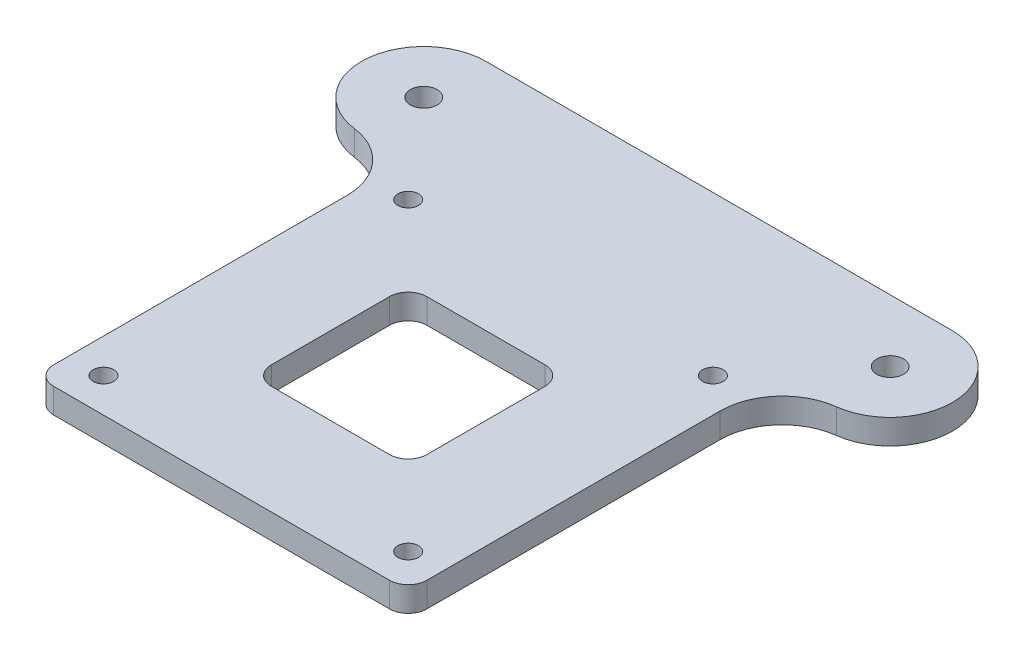
SolidWorks part; units mm, degrees
ref_plane "前视基准面" through (0, 0, 0) normal (0, 0, 1) x (1, 0, 0)
ref_plane "上视基准面" through (0, 0, 0) normal (0, 1, 0) x (1, 0, 0)
ref_plane "右视基准面" through (0, 0, 0) normal (1, 0, 0) x (0, 0, -1)
sketch "Sketch1" plane through (0, 0, 0) normal (0, 1, 0) x (1, 0, 0)
  line L1 (-24.5, -24.5) -> (24.5, -24.5) construction
  line L2 (-24.5, -24.5) -> (-24.5, 24.5) construction
  line L3 (-24.5, 24.5) -> (24.5, 24.5) construction
  line L4 (24.5, -24.5) -> (24.5, 24.5) construction
  line L5 (-24.5, -24.5) -> (24.5, 24.5) construction
  line L6 (-24.5, 24.5) -> (24.5, -24.5) construction
  line L7 (-30, -30) -> (30, -30)
  line L8 (-30, -30) -> (-30, 30)
  line L9 (-30, 30) -> (30, 30)
  line L10 (30, -30) -> (30, 30)
  line L11 (-30, -30) -> (30, 30) construction
  line L12 (-30, 30) -> (30, -30) construction
  circle A0 centre (-24.5, 24.5) radius 1.65
  circle A1 centre (24.5, 24.5) radius 1.65
  circle A2 centre (-24.5, -24.5) radius 1.65
  circle A3 centre (24.5, -24.5) radius 1.65
  point P0 (0, 0)
  point P6 (0, 0)
  dimension "D3" = 3.3
  dimension "D1" = 49
  dimension "D2" = 60
extrude "Boss-Extrude1" add sketch "Sketch1" along normal blind 4
sketch "Sketch2" plane through (0, 4, 0) normal (0, 1, 0) x (1, 0, 0)
  line L0 (-37.5, 40) -> (37.5, 40) construction
  line L1 (-37.5, 50) -> (37.5, 50)
  line L2 (-37.5, 30) -> (37.5, 30)
  line L4 (30, 30) -> (-30, 30) construction
  arc A0 (-37.5, 50) -> (-37.5, 30) centre (-37.5, 40) ccw
  arc A1 (37.5, 30) -> (37.5, 50) centre (37.5, 40) ccw
  circle A2 centre (-37.5, 40) radius 2.15
  circle A3 centre (37.5, 40) radius 2.15
  point P3 (0, 40)
  point P12 (0, 11.6762)
  point P15 (0, 0)
  dimension "D1" = 4.3
  dimension "D2" = 10
  dimension "D3" = 75
extrude "Boss-Extrude2" add sketch "Sketch2" against normal up to surface (4 mm away) up to face at (-24.5, 0, 26.15)
fillet "Fillet1" radius 10 8 edges at (33.75, 4, -30) (-33.75, 4, -30) (-33.75, 0, -30) (-37.5, 2, -30) (33.75, 0, -30) (37.5, 2, -30) (-30, 2, -30) (30, 2, -30)
fillet "Fillet2" radius 3 2 edges at (30, 2, 30) (-30, 2, 30)
sketch "Sketch3" plane through (0, 4, 0) normal (0, 1, 0) x (1, 0, 0)
  line L1 (-12.5, -12.5) -> (12.5, -12.5)
  line L2 (-12.5, -12.5) -> (-12.5, 12.5)
  line L3 (-12.5, 12.5) -> (12.5, 12.5)
  line L4 (12.5, -12.5) -> (12.5, 12.5)
  line L5 (-12.5, -12.5) -> (12.5, 12.5) construction
  line L6 (-12.5, 12.5) -> (12.5, -12.5) construction
  point P0 (0, 0)
  dimension "D1" = 25
extrude "Cut-Extrude1" cut sketch "Sketch3" against normal through all both and the other way through all
fillet "Fillet3" radius 3 4 edges at (12.5, 2, -12.5) (12.5, 2, 12.5) (-12.5, 2, 12.5) (-12.5, 2, -12.5)
